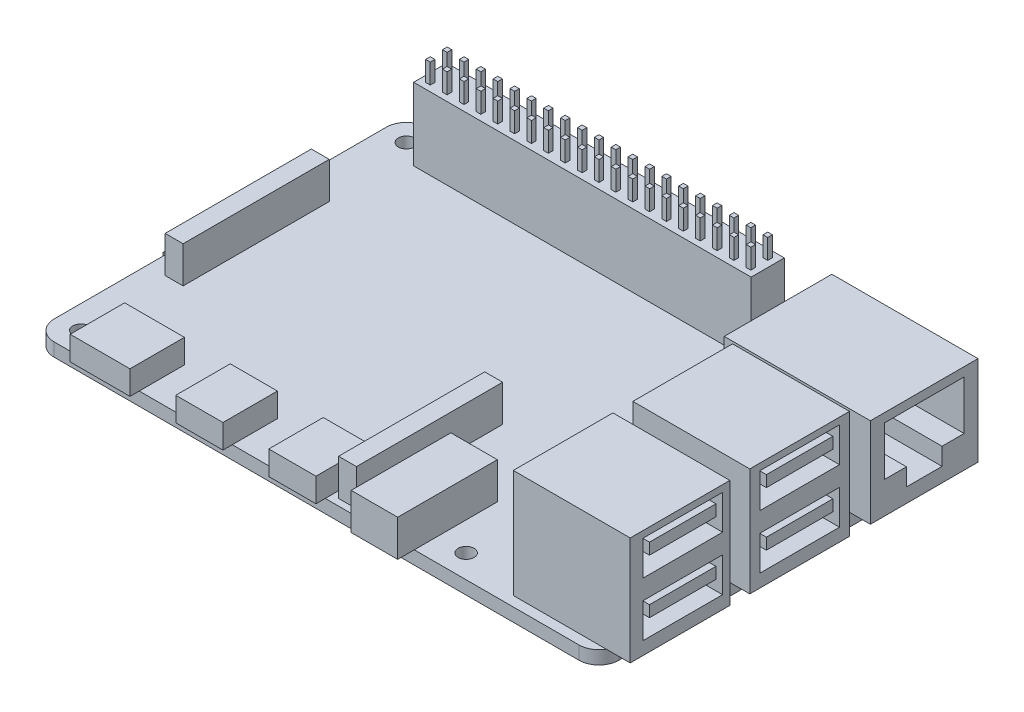
SolidWorks part; units mm, degrees
ref_plane "Plan de face" through (0, 0, 0) normal (0, 0, 1) x (1, 0, 0)
ref_plane "Plan de dessus" through (0, 0, 0) normal (0, 1, 0) x (1, 0, 0)
ref_plane "Plan de droite" through (0, 0, 0) normal (1, 0, 0) x (0, 0, -1)
sketch "Esquisse1" plane through (0, 0, 0) normal (0, 1, 0) x (1, 0, 0)
  line L1 (-42.5, 28) -> (42.5, 28)
  line L2 (-42.5, 28) -> (-42.5, -28)
  line L3 (-42.5, -28) -> (42.5, -28)
  line L4 (42.5, 28) -> (42.5, -28)
  line L5 (-42.5, 28) -> (42.5, -28) construction
  line L6 (-42.5, -28) -> (42.5, 28) construction
  point P0 (0, 0)
  dimension "D1" = 85
  dimension "D2" = 56
extrude "Boss.-Extru.1" add sketch "Esquisse1" along normal blind 2
hole_wizard "Dégagement M21" positions "Esquisse3D1" profile "Esquisse2" hole size "M2" standard "ISO" end condition up to next
sketch3d "Esquisse3D1"
  line L1 (-39, 2, -24.5) -> (-39, 2, 24.5)
  line L2 (-39, 2, -24.5) -> (19, 2, -24.5)
  line L3 (19, 2, -24.5) -> (19, 2, 24.5)
  line L4 (-39, 2, 24.5) -> (19, 2, 24.5)
  line L5 (-42.5, 2, -28) -> (-42.5, 2, 28) construction
  line L6 (42.5, 2, -28) -> (-42.5, 2, -28) construction
  point P0 (-39, 2, -24.5)
  point P2 (-39, 2, 24.5)
  point P4 (19, 2, -24.5)
  point P6 (19, 2, 24.5)
  dimension "D1" = 49
  dimension "D2" = 58
  dimension "D3" = 3.5
  dimension "D4" = 3.5
sketch "Esquisse2" plane through (-39, 2, -24.5) normal (1, 0, 0) x (0, 0, 1)
  line L0 (0, 0) -> (0, 2)
  line L1 (0, 2) -> (1.2, 2)
  line L2 (1.2, 2) -> (1.2, 0)
  line L5 (1.2, 0) -> (0, 0)
  line L11 (0, -6.35) -> (0, 107.95) construction
  dimension "Diamètre du perçage jusqu'au prochain" = 2.4
  dimension "Profondeur du perçage jusqu'au prochain" = 2
sketch "Esquisse4" plane through (0, 2, 0) normal (0, 1, 0) x (1, 0, 0)
  line L0 (-39, 24.5) -> (-35.4, 24.5) construction
  line L1 (-35.4, 27) -> (15.4, 27)
  line L2 (-35.4, 27) -> (-35.4, 22)
  line L3 (-35.4, 22) -> (15.4, 22)
  line L4 (15.4, 27) -> (15.4, 22)
  circle A1 centre (-39, 24.5) radius 1.2 construction
  point P6 (-10, 27)
  dimension "D3" = 29
  dimension "D1" = 5
  dimension "D2" = 50.8
extrude "Boss.-Extru.3" add sketch "Esquisse4" along normal blind 10.9
sketch "Esquisse6" plane through (0, 12.9, 0) normal (0, 1, 0) x (1, 0, 0)
  line L6 (-35.4, 24.5) -> (15.4, 24.5) construction
  line L7 (-11.62, 26.12) -> (-10.92, 26.12)
  line L8 (-11.62, 26.12) -> (-11.62, 25.42)
  line L9 (-11.62, 25.42) -> (-10.92, 25.42)
  line L10 (-10.92, 26.12) -> (-10.92, 25.42)
  line L11 (-35.4, 27) -> (-35.4, 22) construction
  line L12 (15.4, 22) -> (15.4, 27) construction
  line L13 (-10, 27) -> (-10, 22) construction
  line L14 (15.4, 27) -> (-35.4, 27) construction
  line L15 (-35.4, 22) -> (15.4, 22) construction
  line L16 (-8.38, 25.42) -> (-9.08, 25.42)
  line L17 (-9.08, 26.12) -> (-9.08, 25.42)
  line L18 (-8.38, 26.12) -> (-9.08, 26.12)
  line L19 (-8.38, 26.12) -> (-8.38, 25.42)
  line L20 (-8.38, 22.88) -> (-8.38, 23.58)
  line L21 (-8.38, 22.88) -> (-9.08, 22.88)
  line L22 (-9.08, 22.88) -> (-9.08, 23.58)
  line L23 (-8.38, 23.58) -> (-9.08, 23.58)
  line L24 (-11.62, 23.58) -> (-10.92, 23.58)
  line L25 (-10.92, 22.88) -> (-10.92, 23.58)
  line L26 (-11.62, 22.88) -> (-10.92, 22.88)
  line L27 (-11.62, 22.88) -> (-11.62, 23.58)
  line L28 (-14.16, 26.12) -> (-14.16, 25.42)
  line L29 (-14.16, 26.12) -> (-13.46, 26.12)
  line L30 (-13.46, 26.12) -> (-13.46, 25.42)
  line L31 (-14.16, 25.42) -> (-13.46, 25.42)
  line L32 (-16.7, 26.12) -> (-16.7, 25.42)
  line L33 (-16.7, 26.12) -> (-16, 26.12)
  line L34 (-16, 26.12) -> (-16, 25.42)
  line L35 (-16.7, 25.42) -> (-16, 25.42)
  line L36 (-19.24, 26.12) -> (-19.24, 25.42)
  line L37 (-19.24, 26.12) -> (-18.54, 26.12)
  line L38 (-18.54, 26.12) -> (-18.54, 25.42)
  line L39 (-19.24, 25.42) -> (-18.54, 25.42)
  line L40 (-21.78, 26.12) -> (-21.78, 25.42)
  line L41 (-21.78, 26.12) -> (-21.08, 26.12)
  line L42 (-21.08, 26.12) -> (-21.08, 25.42)
  line L43 (-21.78, 25.42) -> (-21.08, 25.42)
  line L44 (-24.32, 26.12) -> (-24.32, 25.42)
  line L45 (-24.32, 26.12) -> (-23.62, 26.12)
  line L46 (-23.62, 26.12) -> (-23.62, 25.42)
  line L47 (-24.32, 25.42) -> (-23.62, 25.42)
  line L48 (-26.86, 26.12) -> (-26.86, 25.42)
  line L49 (-26.86, 26.12) -> (-26.16, 26.12)
  line L50 (-26.16, 26.12) -> (-26.16, 25.42)
  line L51 (-26.86, 25.42) -> (-26.16, 25.42)
  line L52 (-29.4, 26.12) -> (-29.4, 25.42)
  line L53 (-29.4, 26.12) -> (-28.7, 26.12)
  line L54 (-28.7, 26.12) -> (-28.7, 25.42)
  line L55 (-29.4, 25.42) -> (-28.7, 25.42)
  line L56 (-31.94, 26.12) -> (-31.94, 25.42)
  line L57 (-31.94, 26.12) -> (-31.24, 26.12)
  line L58 (-31.24, 26.12) -> (-31.24, 25.42)
  line L59 (-31.94, 25.42) -> (-31.24, 25.42)
  line L60 (-34.48, 26.12) -> (-34.48, 25.42)
  line L61 (-34.48, 26.12) -> (-33.78, 26.12)
  line L62 (-33.78, 26.12) -> (-33.78, 25.42)
  line L63 (-34.48, 25.42) -> (-33.78, 25.42)
  line L64 (-34.48, 23.58) -> (-33.78, 23.58)
  line L65 (-33.78, 22.88) -> (-33.78, 23.58)
  line L66 (-34.48, 22.88) -> (-33.78, 22.88)
  line L67 (-34.48, 22.88) -> (-34.48, 23.58)
  line L68 (-31.94, 23.58) -> (-31.24, 23.58)
  line L69 (-31.24, 22.88) -> (-31.24, 23.58)
  line L70 (-31.94, 22.88) -> (-31.24, 22.88)
  line L71 (-31.94, 22.88) -> (-31.94, 23.58)
  line L72 (-29.4, 23.58) -> (-28.7, 23.58)
  line L73 (-28.7, 22.88) -> (-28.7, 23.58)
  line L74 (-29.4, 22.88) -> (-28.7, 22.88)
  line L75 (-29.4, 22.88) -> (-29.4, 23.58)
  line L76 (-26.86, 23.58) -> (-26.16, 23.58)
  line L77 (-26.16, 22.88) -> (-26.16, 23.58)
  line L78 (-26.86, 22.88) -> (-26.16, 22.88)
  line L79 (-26.86, 22.88) -> (-26.86, 23.58)
  line L80 (-24.32, 23.58) -> (-23.62, 23.58)
  line L81 (-23.62, 22.88) -> (-23.62, 23.58)
  line L82 (-24.32, 22.88) -> (-23.62, 22.88)
  line L83 (-24.32, 22.88) -> (-24.32, 23.58)
  line L84 (-21.78, 23.58) -> (-21.08, 23.58)
  line L85 (-21.08, 22.88) -> (-21.08, 23.58)
  line L86 (-21.78, 22.88) -> (-21.08, 22.88)
  line L87 (-21.78, 22.88) -> (-21.78, 23.58)
  line L88 (-19.24, 23.58) -> (-18.54, 23.58)
  line L89 (-18.54, 22.88) -> (-18.54, 23.58)
  line L90 (-19.24, 22.88) -> (-18.54, 22.88)
  line L91 (-19.24, 22.88) -> (-19.24, 23.58)
  line L92 (-16.7, 23.58) -> (-16, 23.58)
  line L93 (-16, 22.88) -> (-16, 23.58)
  line L94 (-16.7, 22.88) -> (-16, 22.88)
  line L95 (-16.7, 22.88) -> (-16.7, 23.58)
  line L96 (-14.16, 23.58) -> (-13.46, 23.58)
  line L97 (-13.46, 22.88) -> (-13.46, 23.58)
  line L98 (-14.16, 22.88) -> (-13.46, 22.88)
  line L99 (-14.16, 22.88) -> (-14.16, 23.58)
  line L100 (14.48, 25.42) -> (13.78, 25.42)
  line L101 (13.78, 26.12) -> (13.78, 25.42)
  line L102 (14.48, 26.12) -> (13.78, 26.12)
  line L103 (14.48, 26.12) -> (14.48, 25.42)
  line L104 (11.94, 25.42) -> (11.24, 25.42)
  line L105 (11.24, 26.12) -> (11.24, 25.42)
  line L106 (11.94, 26.12) -> (11.24, 26.12)
  line L107 (11.94, 26.12) -> (11.94, 25.42)
  line L108 (9.4, 25.42) -> (8.7, 25.42)
  line L109 (8.7, 26.12) -> (8.7, 25.42)
  line L110 (9.4, 26.12) -> (8.7, 26.12)
  line L111 (9.4, 26.12) -> (9.4, 25.42)
  line L112 (6.86, 25.42) -> (6.16, 25.42)
  line L113 (6.16, 26.12) -> (6.16, 25.42)
  line L114 (6.86, 26.12) -> (6.16, 26.12)
  line L115 (6.86, 26.12) -> (6.86, 25.42)
  line L116 (4.32, 25.42) -> (3.62, 25.42)
  line L117 (3.62, 26.12) -> (3.62, 25.42)
  line L118 (4.32, 26.12) -> (3.62, 26.12)
  line L119 (4.32, 26.12) -> (4.32, 25.42)
  line L120 (1.78, 25.42) -> (1.08, 25.42)
  line L121 (1.08, 26.12) -> (1.08, 25.42)
  line L122 (1.78, 26.12) -> (1.08, 26.12)
  line L123 (1.78, 26.12) -> (1.78, 25.42)
  line L124 (-0.76, 25.42) -> (-1.46, 25.42)
  line L125 (-1.46, 26.12) -> (-1.46, 25.42)
  line L126 (-0.76, 26.12) -> (-1.46, 26.12)
  line L127 (-0.76, 26.12) -> (-0.76, 25.42)
  line L128 (-3.3, 25.42) -> (-4, 25.42)
  line L129 (-4, 26.12) -> (-4, 25.42)
  line L130 (-3.3, 26.12) -> (-4, 26.12)
  line L131 (-3.3, 26.12) -> (-3.3, 25.42)
  line L132 (-5.84, 25.42) -> (-6.54, 25.42)
  line L133 (-6.54, 26.12) -> (-6.54, 25.42)
  line L134 (-5.84, 26.12) -> (-6.54, 26.12)
  line L135 (-5.84, 26.12) -> (-5.84, 25.42)
  line L136 (-5.84, 22.88) -> (-5.84, 23.58)
  line L137 (-5.84, 22.88) -> (-6.54, 22.88)
  line L138 (-6.54, 22.88) -> (-6.54, 23.58)
  line L139 (-5.84, 23.58) -> (-6.54, 23.58)
  line L140 (-3.3, 22.88) -> (-3.3, 23.58)
  line L141 (-3.3, 22.88) -> (-4, 22.88)
  line L142 (-4, 22.88) -> (-4, 23.58)
  line L143 (-3.3, 23.58) -> (-4, 23.58)
  line L144 (-0.76, 22.88) -> (-0.76, 23.58)
  line L145 (-0.76, 22.88) -> (-1.46, 22.88)
  line L146 (-1.46, 22.88) -> (-1.46, 23.58)
  line L147 (-0.76, 23.58) -> (-1.46, 23.58)
  line L148 (1.78, 22.88) -> (1.78, 23.58)
  line L149 (1.78, 22.88) -> (1.08, 22.88)
  line L150 (1.08, 22.88) -> (1.08, 23.58)
  line L151 (1.78, 23.58) -> (1.08, 23.58)
  line L152 (4.32, 22.88) -> (4.32, 23.58)
  line L153 (4.32, 22.88) -> (3.62, 22.88)
  line L154 (3.62, 22.88) -> (3.62, 23.58)
  line L155 (4.32, 23.58) -> (3.62, 23.58)
  line L156 (6.86, 22.88) -> (6.86, 23.58)
  line L157 (6.86, 22.88) -> (6.16, 22.88)
  line L158 (6.16, 22.88) -> (6.16, 23.58)
  line L159 (6.86, 23.58) -> (6.16, 23.58)
  line L160 (9.4, 22.88) -> (9.4, 23.58)
  line L161 (9.4, 22.88) -> (8.7, 22.88)
  line L162 (8.7, 22.88) -> (8.7, 23.58)
  line L163 (9.4, 23.58) -> (8.7, 23.58)
  line L164 (11.94, 22.88) -> (11.94, 23.58)
  line L165 (11.94, 22.88) -> (11.24, 22.88)
  line L166 (11.24, 22.88) -> (11.24, 23.58)
  line L167 (11.94, 23.58) -> (11.24, 23.58)
  line L168 (14.48, 22.88) -> (14.48, 23.58)
  line L169 (14.48, 22.88) -> (13.78, 22.88)
  line L170 (13.78, 22.88) -> (13.78, 23.58)
  line L171 (14.48, 23.58) -> (13.78, 23.58)
  point P30 (-10.92, 25.77)
  point P31 (-10.92, 23.23)
  point P32 (-11.27, 26.12)
  point P33 (-8.73, 26.12)
  dimension "D1" = 0.7
  dimension "D2" = 2.54
  dimension "D3" = 2.54
  dimension "D4" = 10
extrude "Boss.-Extru.5" add sketch "Esquisse6" along normal blind 3
sketch "Esquisse3" plane through (0, 2, 0) normal (0, 1, 0) x (1, 0, 0)
  line L1 (23.7, 25.85) -> (45.7, 25.85)
  line L2 (23.7, 25.85) -> (23.7, 9.65)
  line L3 (28.1, -26.5) -> (45.7, -26.5)
  line L4 (45.7, 25.85) -> (45.7, 9.65)
  line L5 (-42.5, -28) -> (42.5, -28) construction
  line L6 (42.5, -28) -> (42.5, 28) construction
  line L7 (28.1, -11.5) -> (45.7, -11.5)
  line L8 (28.1, -8.5) -> (45.7, -8.5)
  line L9 (28.1, -11.5) -> (28.1, -26.5)
  line L10 (45.7, -11.5) -> (45.7, -26.5)
  line L11 (28.1, 6.5) -> (45.7, 6.5)
  line L12 (23.7, 9.65) -> (45.7, 9.65)
  line L13 (28.1, 6.5) -> (28.1, -8.5)
  line L14 (45.7, 6.5) -> (45.7, -8.5)
  line L15 (45.7, -11.5) -> (45.7, -8.5) construction
  line L16 (45.7, 6.5) -> (45.7, 9.65) construction
  point P4 (23.7, 17.75)
  point P5 (28.1, -1)
  point P18 (28.1, -19)
  line M9 (42.5, -28) -> (42.5, 28)
  dimension "D1" = 45.75
  dimension "D2" = 9
  dimension "D3" = 3.2
  dimension "D4" = 22
  dimension "D5" = 15
  dimension "D6" = 16.2
  dimension "D7" = 17.6
  dimension "D8" = 27
extrude "Boss.-Extru.2" add sketch "Esquisse3" along normal blind 16.3 separate body contours L11 L13 L8 M9 | L7 L9 L3 M9 | L10 L7 L3 M9 | L14 L11 L8 M9 region at (44.1, 2, 19) region at (35.3, 2, 19) region at (44.1, 2, 1) region at (35.3, 2, 1)
extrude "Boss.-Extru.8" add sketch "Esquisse3<3>" along normal blind 13.5 separate body contours L2 L12 L1 M9 | L12 L4 L1 M9 region at (33.1, 2, -17.75) region at (44.1, 2, -17.75)
sketch "Esquisse3<3>" plane through (0, 2, 0) normal (0, 1, 0) x (1, 0, 0) same geometry as "Esquisse3"
sketch "Esquisse7" plane through (45.7, 0, 0) normal (1, 0, 0) x (0, 0, -1)
  line L6 (17.7594, 4.1598) -> (17.7594, 14.1598) construction
  line L7 (23.7594, 14.1598) -> (11.7594, 14.1598)
  line L8 (11.7594, 14.1598) -> (11.7594, 6.7853)
  line L9 (11.7594, 6.7853) -> (15.0804, 6.7853)
  line L10 (15.0804, 6.7853) -> (15.0804, 4.1598)
  line L11 (15.0804, 4.1598) -> (20.4385, 4.1598)
  line L12 (20.4385, 6.7853) -> (20.4385, 4.1598)
  line L13 (23.7594, 6.7853) -> (20.4385, 6.7853)
  line L14 (23.7594, 14.1598) -> (23.7594, 6.7853)
  line L17 (-8.5, 10.15) -> (-3.4275, 10.15) construction
  line L23 (-24.6, 17.3) -> (-24.6, 12.1)
  line L24 (-24.6, 17.3) -> (-12.6, 17.3)
  line L39 (-7, 17.3) -> (5, 17.3)
  line L40 (-7, 17.3) -> (-7, 12.1)
  line L41 (-7, 12.1) -> (5, 12.1)
  line L42 (5, 17.3) -> (5, 12.1)
  line L43 (-6, 16.3) -> (4, 16.3)
  line L44 (-6, 16.3) -> (-6, 14.6)
  line L45 (-6, 14.6) -> (4, 14.6)
  line L46 (4, 16.3) -> (4, 14.6)
  line L47 (-12.6, 17.3) -> (-12.6, 12.1)
  line L48 (-24.6, 12.1) -> (-12.6, 12.1)
  line L49 (-23.6, 16.3) -> (-23.6, 14.6)
  line L50 (-23.6, 16.3) -> (-13.6, 16.3)
  line L51 (-13.6, 16.3) -> (-13.6, 14.6)
  line L52 (-23.6, 14.6) -> (-13.6, 14.6)
  line L53 (-24.6, 9.15) -> (-24.6, 3.95)
  line L54 (-24.6, 9.15) -> (-12.6, 9.15)
  line L55 (-12.6, 9.15) -> (-12.6, 3.95)
  line L56 (-24.6, 3.95) -> (-12.6, 3.95)
  line L57 (-23.6, 8.15) -> (-23.6, 6.45)
  line L58 (-23.6, 8.15) -> (-13.6, 8.15)
  line L59 (-13.6, 8.15) -> (-13.6, 6.45)
  line L60 (-23.6, 6.45) -> (-13.6, 6.45)
  line L61 (-7, 9.15) -> (-7, 3.95)
  line L62 (-7, 9.15) -> (5, 9.15)
  line L63 (5, 9.15) -> (5, 3.95)
  line L64 (-7, 3.95) -> (5, 3.95)
  line L65 (-6, 8.15) -> (-6, 6.45)
  line L66 (-6, 8.15) -> (4, 8.15)
  line L67 (4, 8.15) -> (4, 6.45)
  line L68 (-6, 6.45) -> (4, 6.45)
  point P30 (-1, 14.6)
  point P31 (-1, 12.1)
  dimension "D1" = 12
  dimension "D2" = 10
  dimension "D3" = 12
  dimension "D4" = 5.2
  dimension "D5" = 1.7
  dimension "D6" = 1
  dimension "D8" = 1
  dimension "D9" = 2
  dimension "D10" = 2
extrude "Enlèv. mat.-Extru.1" cut sketch "Esquisse7" against normal blind 12
sketch "Esquisse5" plane through (0, 2, 0) normal (0, 1, 0) x (1, 0, 0)
  line L0 (-42.5, 28) -> (-42.5, -28) construction
  line L5 (-35.7, -21.2) -> (-26.7, -21.2)
  line L6 (-35.7, -21.2) -> (-35.7, -29.4)
  line L7 (-35.7, -29.4) -> (-26.7, -29.4)
  line L8 (-26.7, -21.2) -> (-26.7, -29.4)
  line L9 (-19.8, -21.2) -> (-12.7, -21.2)
  line L10 (-19.8, -21.2) -> (-19.8, -29.4)
  line L11 (-19.8, -29.4) -> (-12.7, -29.4)
  line L12 (-12.7, -21.2) -> (-12.7, -29.4)
  line L13 (-5.8, -21.2) -> (1.3, -21.2)
  line L14 (-5.8, -21.2) -> (-5.8, -29.4)
  line L15 (-5.8, -29.4) -> (1.3, -29.4)
  line L16 (1.3, -21.2) -> (1.3, -29.4)
  line L17 (-42.5, -28) -> (42.5, -28) construction
  dimension "D1" = 6.8
  dimension "D2" = 6.9
  dimension "D3" = 9
  dimension "D4" = 7.1
  dimension "D5" = 6.9
  dimension "D6" = 1.4
  dimension "D7" = 8.2
extrude "Boss.-Extru.4" add sketch "Esquisse5" along normal blind 3.6
sketch "Esquisse8" plane through (0, 2, 0) normal (0, 1, 0) x (1, 0, 0)
  line L0 (1.3, -28) -> (42.5, -28) construction
  line L1 (7.7, -15.5) -> (14.7, -15.5)
  line L2 (7.7, -15.5) -> (7.7, -30.5)
  line L3 (7.7, -30.5) -> (14.7, -30.5)
  line L4 (14.7, -15.5) -> (14.7, -30.5)
  line L5 (42.5, -28) -> (42.5, 28) construction
  line L6 (-42.5, 28) -> (-42.5, -28) construction
  line L7 (5, -27) -> (2.3, -27)
  line L8 (5, -27) -> (5, -5)
  line L9 (5, -5) -> (2.3, -5)
  line L10 (2.3, -27) -> (2.3, -5)
  line L11 (-37.1, -11) -> (-39.8, -11)
  line L12 (-37.1, -11) -> (-37.1, 11)
  line L13 (-37.1, 11) -> (-39.8, 11)
  line L14 (-39.8, -11) -> (-39.8, 11)
  point P18 (-42.5, 0)
  point P19 (-39.8, 0)
  dimension "D1" = 15
  dimension "D2" = 2.5
  dimension "D3" = 27.8
  dimension "D4" = 7
  dimension "D5" = 2.7
  dimension "D6" = 22
  dimension "D7" = 2.7
  dimension "D8" = 2.7
  dimension "D9" = 1
extrude "Boss.-Extru.6" add sketch "Esquisse8" along normal blind 5.5
sketch "Esquisse9" plane through (0, 0, 0) normal (0, -1, 0) x (1, 0, 0)
  line L0 (-42.5, -28) -> (-42.5, 28) construction
  line L1 (-45, 6.1) -> (-29.5, 6.1)
  line L2 (-45, 6.1) -> (-45, -6.1)
  line L3 (-45, -6.1) -> (-29.5, -6.1)
  line L4 (-29.5, 6.1) -> (-29.5, -6.1)
  point P4 (-29.5, 0)
  dimension "D1" = 12.2
  dimension "D2" = 15.5
  dimension "D3" = 2.5
extrude "Boss.-Extru.7" add sketch "Esquisse9" along normal blind 1.5
fillet "Congé1" radius 3 4 edges at (42.5, 1, 28) (42.5, 1, -28) (-42.5, 1, 28) (-42.5, 1, -28)
ref_plane "Plan1" through (-31.2, 0, 0) normal (1, 0, 0) x (0, 0, -1)
ref_plane "Plan2" through (0, 3.8, 0) normal (0, 1, 0) x (1, 0, 0)
ref_plane "Plan3" through (0, 0, -17.75) normal (0, 0, 1) x (1, 0, 0)
ref_plane "Plan4" through (0, 10.4725, 0) normal (0, 1, 0) x (1, 0, 0)
equation "\"D5@Esquisse5\"=\"D2@Esquisse5\""
equation "\"D3@Esquisse6\"=\"D2@Esquisse6\""
